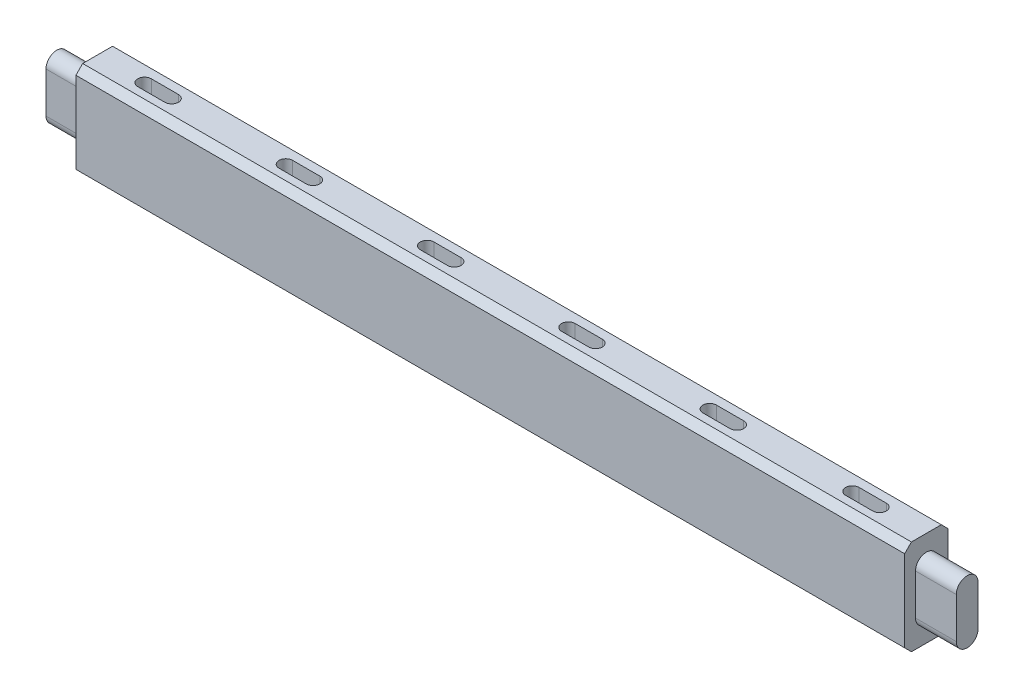
SolidWorks part; units mm, degrees
ref_plane "Front" through (0, 0, 0) normal (0, 0, 1) x (1, 0, 0)
ref_plane "Top" through (0, 0, 0) normal (0, 1, 0) x (1, 0, 0)
ref_plane "Right" through (0, 0, 0) normal (1, 0, 0) x (0, 0, -1)
sketch "Esquisse1" plane through (0, 0, 0) normal (0, 0, 1) x (1, 0, 0)
  line L1 (0, 0) -> (610, 0)
  line L2 (0, 0) -> (0, 70)
  line L3 (0, 70) -> (610, 70)
  line L4 (610, 0) -> (610, 70)
  dimension "D1" = 610
  dimension "D2" = 70
extrude "Boss.-Extru.1" add sketch "Esquisse1" along normal blind 32
sketch "Esquisse2" plane through (0, 0, 0) normal (-1, 0, 0) x (0, 0, 1)
  line L0 (16, 0) -> (16, 70) construction
  line L1 (32, 0) -> (0, 0) construction
  line L2 (32, 70) -> (0, 70) construction
  line L3 (16, 20) -> (16, 50) construction
  line L4 (8, 20) -> (8, 50)
  line L5 (24, 20) -> (24, 50)
  arc A0 (8, 20) -> (24, 20) centre (16, 20) ccw
  arc A1 (24, 50) -> (8, 50) centre (16, 50) ccw
  point P8 (16, 35)
  dimension "D1" = 16
  dimension "D2" = 30
extrude "Boss.-Extru.2" add sketch "Esquisse2" along normal blind 30
extrude "Boss.-Extru.3" add sketch "Esquisse2<2>" against normal blind 30 from vertex starting at point (610, 70, 0)
sketch "Esquisse2<2>" plane through (0, 0, 0) normal (-1, 0, 0) x (0, 0, 1) same geometry as "Esquisse2"
chamfer "Chanfrein1" distance 5 angle 45 4 edges at (305, 0, 32) (305, 0, 0) (305, 70, 0) (305, 70, 32)
sketch "Esquisse3" [suppressed] plane through (0, 80, 0) normal (0, 1, 0) x (1, 0, 0)
  line L0 (305, -27) -> (305, -5) construction
  line L1 (0, -27) -> (610, -27) construction
  line L2 (305, -16) -> (415, -16) construction
  line L3 (360, -16) -> (360, -5) construction
  line L4 (610, -5) -> (0, -5) construction
  line L7 (305, -16) -> (195, -16) construction
  line L8 (185, -16) -> (205, -16) construction
  line L9 (185, -11) -> (205, -11)
  line L10 (185, -21) -> (205, -21)
  line L11 (82, -16) -> (102, -16) construction
  line L12 (82, -11) -> (102, -11)
  line L13 (82, -21) -> (102, -21)
  line L14 (-21, -16) -> (-1, -16) construction
  line L15 (-21, -11) -> (-1, -11)
  line L16 (-21, -21) -> (-1, -21)
  line L17 (-124, -16) -> (-104, -16) construction
  line L18 (-124, -11) -> (-104, -11)
  line L19 (-124, -21) -> (-104, -21)
  line L20 (-227, -16) -> (-207, -16) construction
  line L21 (-227, -11) -> (-207, -11)
  line L22 (-227, -21) -> (-207, -21)
  line L23 (595, -16) -> (315, -16) construction
  line L24 (595, -16) -> (315, -16) construction
  line L25 (295, -16) -> (315, -16) construction
  line L26 (295, -11) -> (315, -11)
  line L27 (295, -21) -> (315, -21)
  line L29 (837, -16) -> (817, -16) construction
  line L30 (837, -11) -> (817, -11)
  line L31 (837, -21) -> (817, -21)
  line L32 (734, -16) -> (714, -16) construction
  line L33 (734, -11) -> (714, -11)
  line L34 (734, -21) -> (714, -21)
  line L35 (631, -16) -> (611, -16) construction
  line L36 (631, -11) -> (611, -11)
  line L37 (631, -21) -> (611, -21)
  line L38 (528, -16) -> (508, -16) construction
  line L39 (528, -11) -> (508, -11)
  line L40 (528, -21) -> (508, -21)
  line L41 (425, -16) -> (405, -16) construction
  line L42 (425, -11) -> (405, -11)
  line L43 (425, -21) -> (405, -21)
  line L89 (-65, -16) -> (-45, -16) construction
  line L90 (-65, -11) -> (-45, -11)
  line L91 (-65, -21) -> (-45, -21)
  line L92 (-330, -16) -> (-310, -16) construction
  line L93 (-330, -11) -> (-310, -11)
  line L94 (-330, -21) -> (-310, -21)
  arc A0 (185, -11) -> (185, -21) centre (185, -16) ccw
  arc A1 (205, -21) -> (205, -11) centre (205, -16) ccw
  arc A2 (82, -11) -> (82, -21) centre (82, -16) ccw
  arc A3 (102, -21) -> (102, -11) centre (102, -16) ccw
  arc A4 (-21, -11) -> (-21, -21) centre (-21, -16) ccw
  arc A5 (-1, -21) -> (-1, -11) centre (-1, -16) ccw
  arc A6 (-124, -11) -> (-124, -21) centre (-124, -16) ccw
  arc A7 (-104, -21) -> (-104, -11) centre (-104, -16) ccw
  arc A8 (-227, -11) -> (-227, -21) centre (-227, -16) ccw
  arc A9 (-207, -21) -> (-207, -11) centre (-207, -16) ccw
  arc A10 (295, -11) -> (295, -21) centre (295, -16) ccw
  arc A11 (315, -21) -> (315, -11) centre (315, -16) ccw
  arc A14 (837, -11) -> (837, -21) centre (837, -16) cw
  arc A15 (817, -21) -> (817, -11) centre (817, -16) cw
  arc A16 (734, -11) -> (734, -21) centre (734, -16) cw
  arc A17 (714, -21) -> (714, -11) centre (714, -16) cw
  arc A18 (631, -11) -> (631, -21) centre (631, -16) cw
  arc A19 (611, -21) -> (611, -11) centre (611, -16) cw
  arc A20 (528, -11) -> (528, -21) centre (528, -16) cw
  arc A21 (508, -21) -> (508, -11) centre (508, -16) cw
  arc A22 (425, -11) -> (425, -21) centre (425, -16) cw
  arc A23 (405, -21) -> (405, -11) centre (405, -16) cw
  arc A56 (-330, -11) -> (-330, -21) centre (-330, -16) ccw
  arc A57 (-310, -21) -> (-310, -11) centre (-310, -16) ccw
  point P10 (195, -16)
  point P19 (92, -16)
  point P26 (-11, -16)
  point P33 (-114, -16)
  point P40 (-217, -16)
  point P49 (305, -16)
  point P59 (827, -16)
  point P66 (724, -16)
  point P73 (621, -16)
  point P80 (518, -16)
  point P87 (415, -16)
  point P94 (-11, -16)
  point P104 (-11, -16)
  point P111 (-11, -16)
  point P118 (-11, -16)
  point P125 (-16, -16)
  point P132 (-16, -16)
  point P139 (-16, -16)
  point P146 (-16, -16)
  point P153 (-55, -16)
  point P160 (-55, -16)
  point P167 (-55, -16)
  point P174 (-55, -16)
  point P181 (-55, -16)
  point P188 (-55, -16)
  point P195 (-55, -16)
  point P202 (-55, -16)
  point P209 (-320, -16)
  dimension "D1" = 10
  dimension "D2" = 208
  dimension "D3" = 20
  dimension "D4" = 6
  dimension "D5" = 104
extrude "Enlèv. mat.-Extru.1" [suppressed] cut sketch "Esquisse3" against normal blind 15
sketch "Esquisse5" plane through (0, 70, 0) normal (0, 1, 0) x (1, 0, 0)
  line L0 (253, -27.4919) -> (253, -5.4919) construction
  line L2 (253, -16.4919) -> (357, -16.4919) construction
  line L3 (305, -16.4919) -> (305, -5) construction
  line L5 (610, -5) -> (0, -5) construction
  line L7 (253, -16.4919) -> (149, -16.4919) construction
  line L8 (139, -16.4919) -> (159, -16.4919) construction
  line L9 (139, -11.4919) -> (159, -11.4919)
  line L10 (139, -21.4919) -> (159, -21.4919)
  line L11 (35, -16.4919) -> (55, -16.4919) construction
  line L12 (35, -11.4919) -> (55, -11.4919)
  line L13 (35, -21.4919) -> (55, -21.4919)
  line L23 (383.7577, -16.4919) -> (263, -16.4919) construction
  line L24 (383.7577, -16.4919) -> (263, -16.4919) construction
  line L25 (243, -16.4919) -> (263, -16.4919) construction
  line L26 (243, -11.4919) -> (263, -11.4919)
  line L27 (243, -21.4919) -> (263, -21.4919)
  line L35 (576, -16.4919) -> (556, -16.4919) construction
  line L36 (576, -11.4919) -> (556, -11.4919)
  line L37 (576, -21.4919) -> (556, -21.4919)
  line L38 (471, -16.4919) -> (451, -16.4919) construction
  line L39 (471, -11.4919) -> (451, -11.4919)
  line L40 (471, -21.4919) -> (451, -21.4919)
  line L41 (367, -16.4919) -> (347, -16.4919) construction
  line L42 (367, -11.4919) -> (347, -11.4919)
  line L43 (367, -21.4919) -> (347, -21.4919)
  line L245 (-67, -16.4919) -> (-47, -16.4919) construction
  line L246 (-67, -11.4919) -> (-47, -11.4919)
  line L247 (-67, -21.4919) -> (-47, -21.4919)
  line L248 (-170, -16.4919) -> (-150, -16.4919) construction
  line L249 (-170, -11.4919) -> (-150, -11.4919)
  line L250 (-170, -21.4919) -> (-150, -21.4919)
  line L251 (-273, -16.4919) -> (-253, -16.4919) construction
  line L252 (-273, -11.4919) -> (-253, -11.4919)
  line L253 (-273, -21.4919) -> (-253, -21.4919)
  line L254 (-376, -16.4919) -> (-356, -16.4919) construction
  line L255 (-376, -11.4919) -> (-356, -11.4919)
  line L256 (-376, -21.4919) -> (-356, -21.4919)
  line L257 (-69, -16.4919) -> (-49, -16.4919) construction
  line L258 (-69, -11.4919) -> (-49, -11.4919)
  line L259 (-69, -21.4919) -> (-49, -21.4919)
  line L260 (-173, -16.4919) -> (-153, -16.4919) construction
  line L261 (-173, -11.4919) -> (-153, -11.4919)
  line L262 (-173, -21.4919) -> (-153, -21.4919)
  line L263 (-277, -16.4919) -> (-257, -16.4919) construction
  line L264 (-277, -11.4919) -> (-257, -11.4919)
  line L265 (-277, -21.4919) -> (-257, -21.4919)
  line L266 (-381, -16.4919) -> (-361, -16.4919) construction
  line L267 (-381, -11.4919) -> (-361, -11.4919)
  line L268 (-381, -21.4919) -> (-361, -21.4919)
  arc A0 (139, -11.4919) -> (139, -21.4919) centre (139, -16.4919) ccw
  arc A1 (159, -21.4919) -> (159, -11.4919) centre (159, -16.4919) ccw
  arc A2 (35, -11.4919) -> (35, -21.4919) centre (35, -16.4919) ccw
  arc A3 (55, -21.4919) -> (55, -11.4919) centre (55, -16.4919) ccw
  arc A10 (243, -11.4919) -> (243, -21.4919) centre (243, -16.4919) ccw
  arc A11 (263, -21.4919) -> (263, -11.4919) centre (263, -16.4919) ccw
  arc A18 (576, -11.4919) -> (576, -21.4919) centre (576, -16.4919) cw
  arc A19 (556, -21.4919) -> (556, -11.4919) centre (556, -16.4919) cw
  arc A20 (471, -11.4919) -> (471, -21.4919) centre (471, -16.4919) cw
  arc A21 (451, -21.4919) -> (451, -11.4919) centre (451, -16.4919) cw
  arc A22 (367, -11.4919) -> (367, -21.4919) centre (367, -16.4919) cw
  arc A23 (347, -21.4919) -> (347, -11.4919) centre (347, -16.4919) cw
  arc A166 (-69, -11.4919) -> (-69, -21.4919) centre (-69, -16.4919) ccw
  arc A167 (-49, -21.4919) -> (-49, -11.4919) centre (-49, -16.4919) ccw
  arc A168 (-173, -11.4919) -> (-173, -21.4919) centre (-173, -16.4919) ccw
  arc A169 (-153, -21.4919) -> (-153, -11.4919) centre (-153, -16.4919) ccw
  arc A170 (-277, -11.4919) -> (-277, -21.4919) centre (-277, -16.4919) ccw
  arc A171 (-257, -21.4919) -> (-257, -11.4919) centre (-257, -16.4919) ccw
  arc A172 (-381, -11.4919) -> (-381, -21.4919) centre (-381, -16.4919) ccw
  arc A173 (-361, -21.4919) -> (-361, -11.4919) centre (-361, -16.4919) ccw
  point P4 (305, -5)
  point P10 (149, -16.4919)
  point P19 (45, -16.4919)
  point P26 (-169, -16.4919)
  point P33 (-272, -16.4919)
  point P49 (253, -16.4919)
  point P55 (-66, -16.4919)
  point P73 (566, -16.4919)
  point P80 (461, -16.4919)
  point P87 (357, -16.4919)
  point P94 (-225.2423, -16.4919)
  point P104 (-225.2423, -16.4919)
  point P111 (-225.2423, -16.4919)
  point P118 (-225.2423, -16.4919)
  point P125 (-230.2423, -16.4919)
  point P132 (-230.2423, -16.4919)
  point P139 (-230.2423, -16.4919)
  point P146 (-230.2423, -16.4919)
  point P153 (-269.2423, -16.4919)
  point P160 (-269.2423, -16.4919)
  point P167 (-269.2423, -16.4919)
  point P174 (-269.2423, -16.4919)
  point P181 (-269.2423, -16.4919)
  point P188 (-269.2423, -16.4919)
  point P195 (-269.2423, -16.4919)
  point P202 (-269.2423, -16.4919)
  point P209 (-534.2423, -16.4919)
  point P216 (-534.2423, -16.4919)
  point P223 (-375, -16.4919)
  point P230 (-66, -16.4919)
  point P237 (-169, -16.4919)
  point P244 (-272, -16.4919)
  point P251 (-375, -16.4919)
  point P258 (-66, -16.4919)
  point P265 (-169, -16.4919)
  point P272 (-272, -16.4919)
  point P279 (-375, -16.4919)
  point P286 (-66, -16.4919)
  point P293 (-169, -16.4919)
  point P300 (-272, -16.4919)
  point P307 (-375, -16.4919)
  point P314 (-66, -16.4919)
  point P321 (-169, -16.4919)
  point P328 (-272, -16.4919)
  point P335 (-375, -16.4919)
  point P342 (-66, -16.4919)
  point P349 (-169, -16.4919)
  point P356 (-272, -16.4919)
  point P363 (-375, -16.4919)
  point P370 (-66, -16.4919)
  point P377 (-169, -16.4919)
  point P384 (-272, -16.4919)
  point P391 (-375, -16.4919)
  point P398 (-66, -16.4919)
  point P405 (-169, -16.4919)
  point P412 (-272, -16.4919)
  point P419 (-375, -16.4919)
  point P426 (-66, -16.4919)
  point P433 (-169, -16.4919)
  point P440 (-272, -16.4919)
  point P447 (-375, -16.4919)
  point P454 (-66, -16.4919)
  point P461 (-169, -16.4919)
  point P468 (-272, -16.4919)
  point P475 (-375, -16.4919)
  point P482 (-55.5, -16.4919)
  point P489 (-158.5, -16.4919)
  point P496 (-261.5, -16.4919)
  point P503 (-364.5, -16.4919)
  point P510 (-55.5, -16.4919)
  point P517 (-158.5, -16.4919)
  point P524 (-261.5, -16.4919)
  point P531 (-364.5, -16.4919)
  point P538 (-57, -16.4919)
  point P545 (-160, -16.4919)
  point P552 (-263, -16.4919)
  point P559 (-366, -16.4919)
  point P566 (-57, -16.4919)
  point P573 (-160, -16.4919)
  point P580 (-263, -16.4919)
  point P587 (-366, -16.4919)
  point P594 (-59, -16.4919)
  point P601 (-163, -16.4919)
  point P608 (-267, -16.4919)
  point P615 (-371, -16.4919)
  dimension "D1" = 10
  dimension "D2" = 208
  dimension "D3" = 20
  dimension "D4" = 6
  dimension "D5" = 104
extrude "Enlèv. mat.-Extru.2" cut sketch "Esquisse5" against normal blind 15
